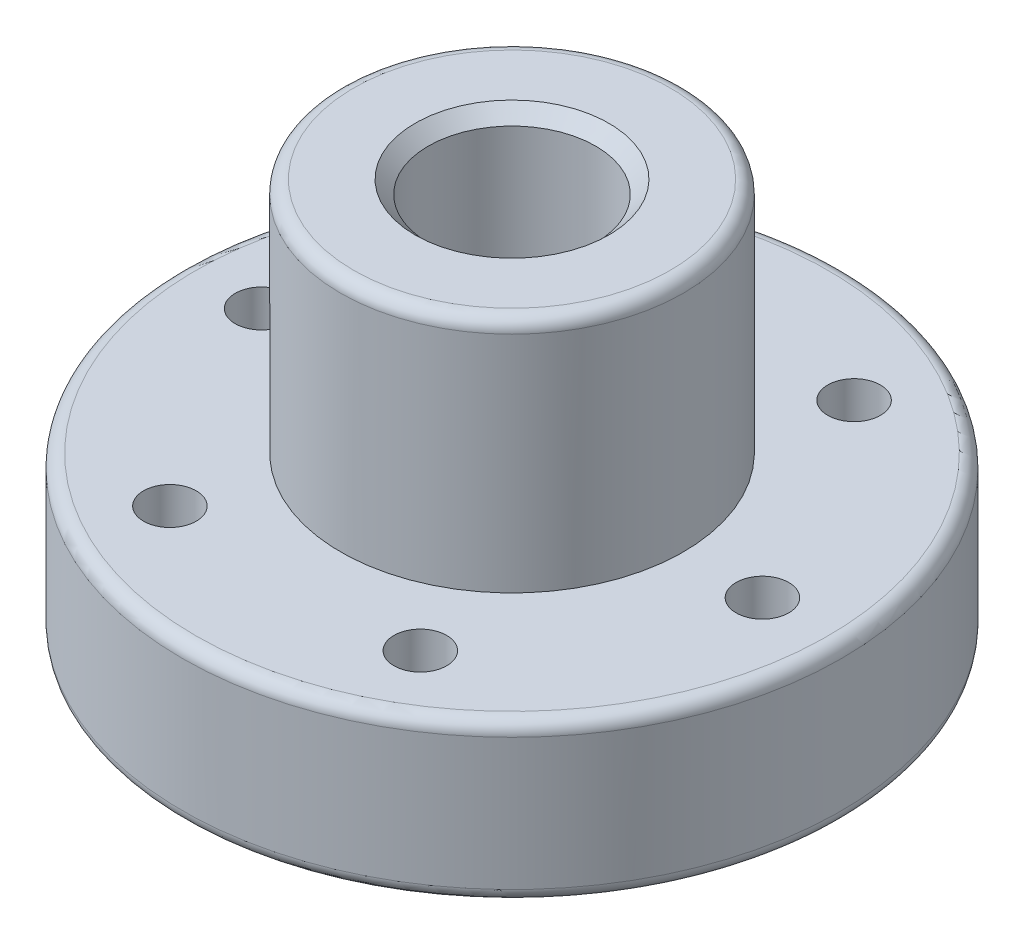
SolidWorks part; units mm, degrees
ref_plane "Plan de face" through (0, 0, 0) normal (0, 0, 1) x (1, 0, 0)
ref_plane "Plan de dessus" through (0, 0, 0) normal (0, 1, 0) x (1, 0, 0)
ref_plane "Plan de droite" through (0, 0, 0) normal (1, 0, 0) x (0, 0, -1)
sketch "Esquisse1" plane through (0, 0, 0) normal (0, 0, 1) x (1, 0, 0)
  line L0 (6.5, 15) -> (6.5, 6)
  line L1 (6.5, 6) -> (12.5, 6)
  line L2 (12.5, 6) -> (12.5, 0)
  line L9 (6.5, 15) -> (3.175, 15)
  line L10 (3.175, 15) -> (3.175, 0)
  line L11 (12.5, 0) -> (3.175, 0)
  line L12 (0, 0) -> (0, 15) construction
  dimension "D1" = 12.5
  dimension "D2" = 6
  dimension "D3" = 15
  dimension "D4" = 3.175
  dimension "D5" = 6
  dimension "D6" = 9.325
revolve "Révolution2" add sketch "Esquisse1" angle 360 about L12
sketch "Esquisse3" plane through (0, 6, 0) normal (0, 1, 0) x (1, 0, 0)
  line L0 (0, 0) -> (9.5, 0) construction
  circle A0 centre (9.5, 0) radius 1
  circle A2 centre (0, 0) radius 12.5 construction
  circle A3 centre (0, 0) radius 6.5 construction
  circle A11 centre (4.75, -8.2272) radius 1
  circle A12 centre (-4.75, -8.2272) radius 1
  circle A13 centre (-9.5, 0) radius 1
  circle A14 centre (-4.75, 8.2272) radius 1
  circle A15 centre (4.75, 8.2272) radius 1
  point P7 (6.5, 0)
  point P8 (12.5, 0)
  point P19 (0, 0)
  point P23 (0, -4.027)
  point P24 (0, 0)
  dimension "D1" = 2
  dimension "D3" = 3
  dimension "D2" = 3
  dimension "D4" = 6
extrude "Enlèv. mat.-Extru.1" cut sketch "Esquisse3" against normal through all
fillet "Congé1" radius 0.5 3 edges at (0, 15, -6.5) (0, 0, -12.5) (0, 6, -12.5)
chamfer "Chanfrein1" distance 0.5 angle 45 2 edges at (0, 0, -3.175) (0, 15, -3.175)
sketch "Esquisse8" [suppressed] plane through (0, -5.2608, 0) normal (0, 1, 0) x (1, 0, 0)
  circle A0 centre (8, 0) radius 0.8
  circle A4 centre (0, -8) radius 0.8
  circle A5 centre (-8, 0) radius 0.8
  circle A6 centre (0, 8) radius 0.8
  point P12 (0, 0)
  dimension "D1" = 1.6
  dimension "D3" = 4
  dimension "D2" = 8
extrude "Enlèv. mat.-Extru.2" [suppressed] cut sketch "Esquisse8" against normal through all
